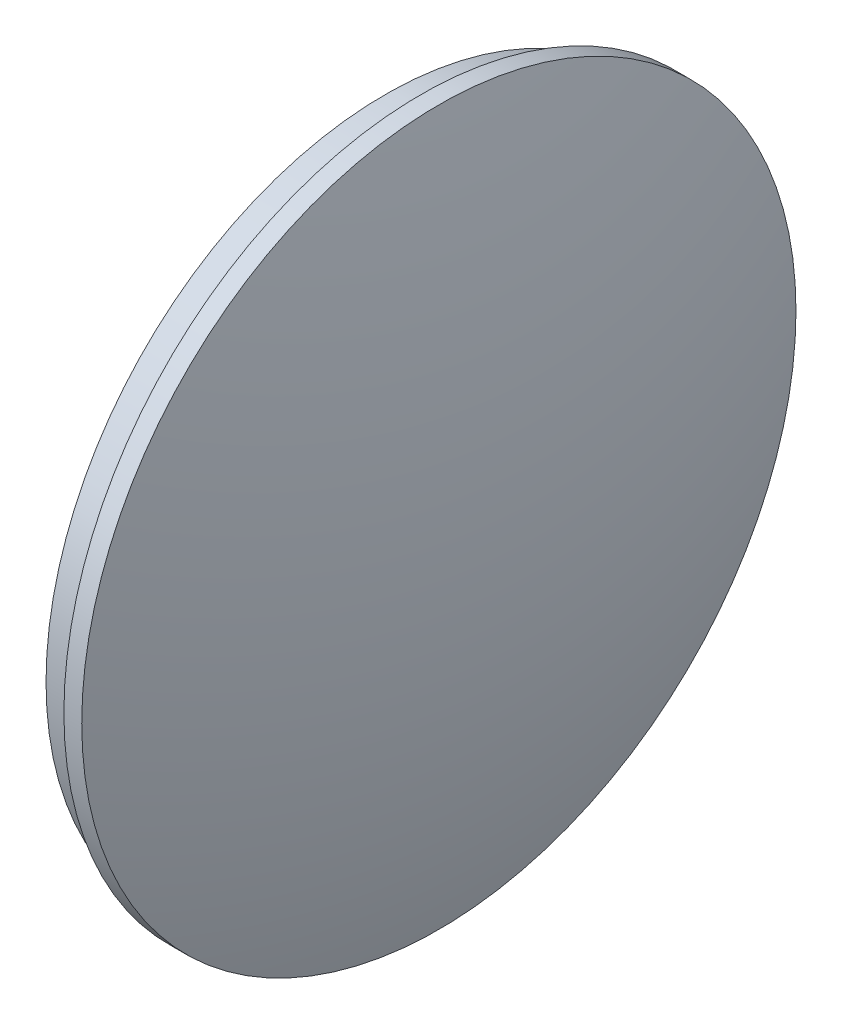
SolidWorks part; units mm, degrees
ref_plane "Front Plane" through (0, 0, 0) normal (0, 0, 1) x (1, 0, 0)
ref_plane "Top Plane" through (0, 0, 0) normal (0, 1, 0) x (1, 0, 0)
ref_plane "Right Plane" through (0, 0, 0) normal (1, 0, 0) x (0, 0, -1)
sketch "Sketch1" plane through (0, 0, 0) normal (0, 0, 1) x (1, 0, 0)
  line L0 (0, 0) -> (0, 20)
  line L1 (0, 20) -> (-1, 20)
  line L2 (-1, 20) -> (-1, 19)
  line L3 (-1, 19) -> (-3, 19)
  line L4 (-3, 19) -> (-3, 0)
  line L5 (-3, 0) -> (0, 0)
  dimension "D1" = 19
  dimension "D2" = 20
  dimension "D3" = 1
  dimension "D4" = 3
revolve "Revolve1" add sketch "Sketch1" angle 360 about L5
dome "Dome1" faces to dome 1 distance 3 reverse direction no elliptical dome no face at (0, 0, 20) parameters "D1"=3
